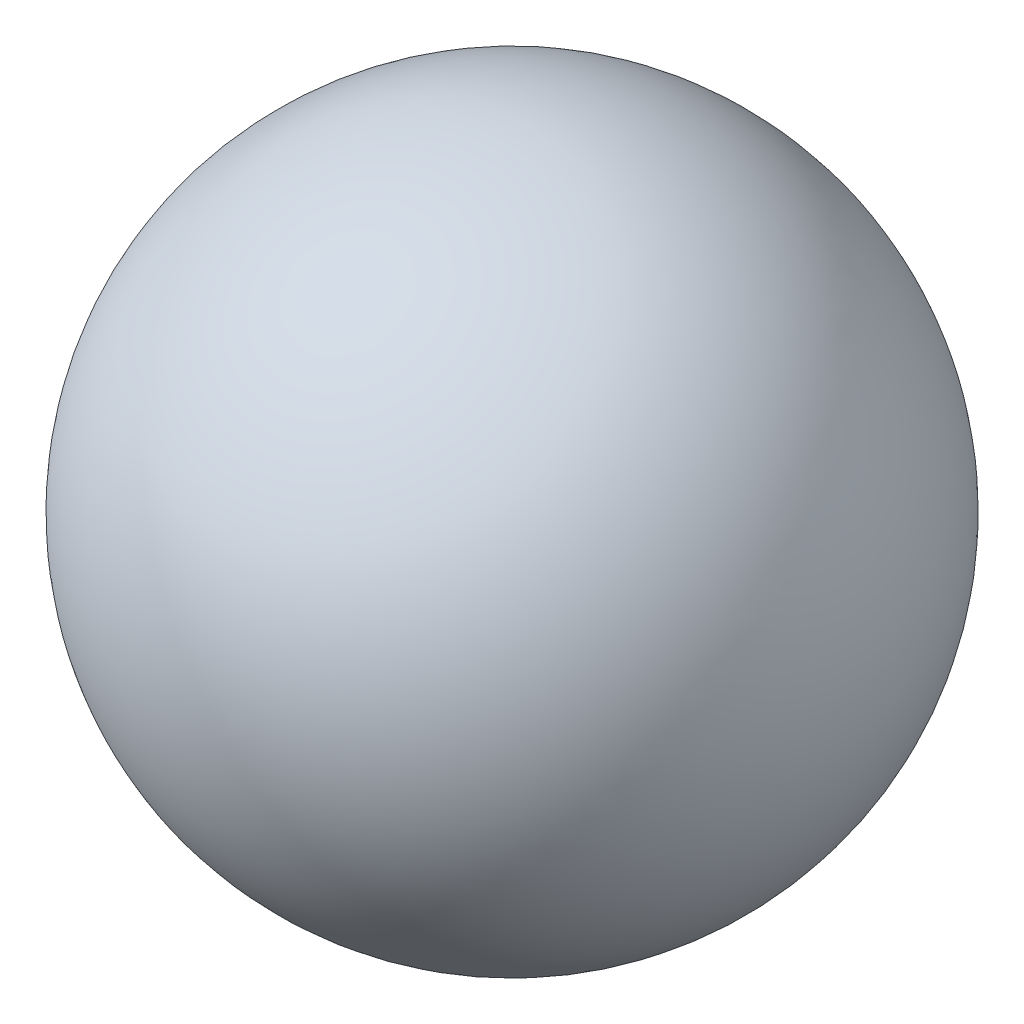
SolidWorks part; units mm, degrees
ref_plane "前视基准面" through (0, 0, 0) normal (0, 0, 1) x (1, 0, 0)
ref_plane "上视基准面" through (0, 0, 0) normal (0, 1, 0) x (1, 0, 0)
ref_plane "右视基准面" through (0, 0, 0) normal (1, 0, 0) x (0, 0, -1)
sketch "草图1" plane through (0, 0, 0) normal (0, 1, 0) x (1, 0, 0)
  line L0 (0, 0) -> (0, 19.4076) construction
  line L1 (0, 8.5) -> (0, -8.5)
  arc A0 (0, 8.5) -> (0, -8.5) centre (0, 0) ccw
revolve "旋转4" add sketch "草图1" angle 360 about L0
